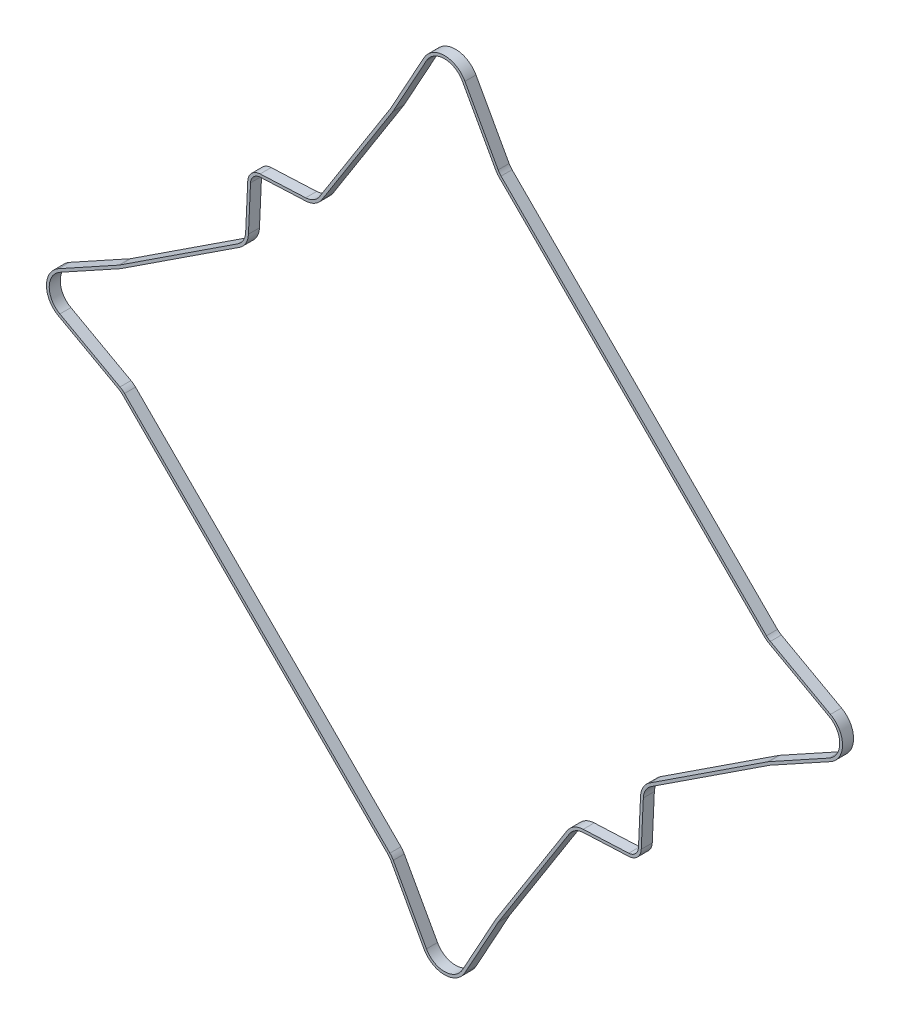
SolidWorks part; units mm, degrees
material "NEOPRENE"
ref_plane "Front Plane" through (0, 0, 0) normal (0, 0, 1) x (1, 0, 0)
ref_plane "Top Plane" through (0, 0, 0) normal (0, 1, 0) x (1, 0, 0)
ref_plane "Right Plane" through (0, 0, 0) normal (1, 0, 0) x (0, 0, -1)
sketch "Sketch2" plane through (0, 0, 0) normal (0, 0, 1) x (1, 0, 0)
  line L0 (0, 0) -> (1, 0) construction
  line L1 (0, 0) -> (0, 1) construction
  line L2 (9.6324, -5.3119) -> (27.6801, 27.4153)
  line L3 (47.3199, 27.4153) -> (65.3676, -5.3119)
  line L4 (67.2218, -7.7782) -> (211.7218, -152.2782)
  line L5 (214.1881, -154.1324) -> (246.9153, -172.1801)
  line L6 (246.9153, -191.8199) -> (214.1881, -209.8676)
  line L7 (213.4705, -210.2997) -> (149.2041, -252.417)
  line L8 (144.245, -261.1155) -> (143.1126, -285.9127)
  line L9 (137.8097, -291.2156) -> (113.0125, -292.348)
  line L10 (104.2278, -297.4407) -> (65.7135, -358.1041)
  line L11 (65.3676, -358.6881) -> (47.3199, -391.4153)
  line L12 (27.6801, -391.4153) -> (9.6324, -358.6881)
  line L13 (7.7782, -356.2218) -> (-136.7218, -211.7218)
  line L14 (-139.1881, -209.8676) -> (-171.9153, -191.8199)
  line L15 (-171.9153, -172.1801) -> (-139.1881, -154.1324)
  line L17 (-138.4705, -153.7003) -> (-74.2041, -111.583)
  line L18 (-69.245, -102.8845) -> (-68.1126, -78.0873)
  line L19 (-62.8097, -72.7844) -> (-38.0125, -71.652)
  line L20 (-29.2278, -66.5593) -> (9.2865, -5.8959)
  arc A0 (9.2865, -5.8959) -> (9.6324, -5.3119) centre (0, 0) ccw
  arc A1 (27.6801, 27.4153) -> (47.3199, 27.4153) centre (37.5, 22) cw
  arc A2 (65.3676, -5.3119) -> (67.2218, -7.7782) centre (75, 0) ccw
  arc A3 (211.7218, -152.2782) -> (214.1881, -154.1324) centre (219.5, -144.5) ccw
  arc A4 (246.9153, -172.1801) -> (246.9153, -191.8199) centre (241.5, -182) cw
  arc A5 (214.1881, -209.8676) -> (213.4705, -210.2997) centre (219.5, -219.5) ccw
  arc A6 (149.2041, -252.417) -> (144.245, -261.1155) centre (155.2336, -261.6173) ccw
  arc A7 (143.1126, -285.9127) -> (137.8097, -291.2156) centre (137.5559, -285.6589) cw
  arc A8 (113.0125, -292.348) -> (104.2278, -297.4407) centre (113.5143, -303.3366) ccw
  arc A9 (65.7135, -358.1041) -> (65.3676, -358.6881) centre (75, -364) ccw
  arc A10 (47.3199, -391.4153) -> (27.6801, -391.4153) centre (37.5, -386) cw
  arc A11 (9.6324, -358.6881) -> (7.7782, -356.2218) centre (0, -364) ccw
  arc A12 (-136.7218, -211.7218) -> (-139.1881, -209.8676) centre (-144.5, -219.5) ccw
  arc A13 (-171.9153, -191.8199) -> (-171.9153, -172.1801) centre (-166.5, -182) cw
  arc A14 (-139.1881, -154.1324) -> (-138.4705, -153.7003) centre (-144.5, -144.5) ccw
  arc A15 (-74.2041, -111.583) -> (-69.245, -102.8845) centre (-80.2336, -102.3827) ccw
  arc A16 (-68.1126, -78.0873) -> (-62.8097, -72.7844) centre (-62.5559, -78.3411) cw
  arc A17 (-38.0125, -71.652) -> (-29.2278, -66.5593) centre (-38.5143, -60.6634) ccw
extrude "Extrude-Thin1" add sketch "Sketch2" along normal mid plane 6 thin thin type one direction wall 1.52
